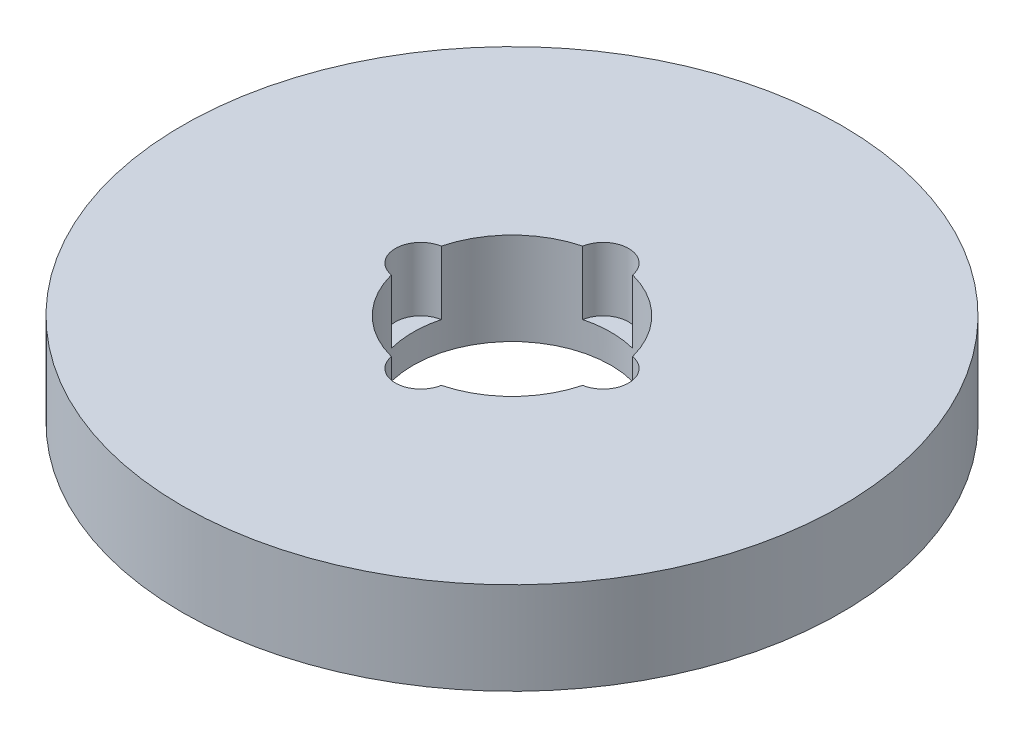
SolidWorks part; units mm, degrees
ref_plane "Front Plane" through (0, 0, 0) normal (0, 0, 1) x (1, 0, 0)
ref_plane "Top Plane" through (0, 0, 0) normal (0, 1, 0) x (1, 0, 0)
ref_plane "Right Plane" through (0, 0, 0) normal (1, 0, 0) x (0, 0, -1)
sketch "Sketch1" plane through (0, 0, 0) normal (0, 1, 0) x (1, 0, 0)
  circle A0 centre (0, 0) radius 25
  dimension "FLANGE_OD" = 50
extrude "Boss-Extrude1" add sketch "Sketch1" along normal blind 7
sketch "Sketch2" plane through (0, 0, 0) normal (0, 1, 0) x (1, 0, 0)
  circle A0 centre (0, 0) radius 7.5
  dimension "BORE_D" = 15
extrude "Cut-Extrude1" cut sketch "Sketch2" along normal through all
sketch "Sketch3" plane through (0, 7, 0) normal (0, 1, 0) x (1, 0, 0)
  circle A0 centre (0, 0) radius 6.9221 construction
  circle A1 centre (-6.9221, 0) radius 1.9224
  dimension "BOLT_D" = 3.8449
  dimension "BOLT_PCD" = 13.8442
extrude "Cut-Extrude2" cut sketch "Sketch3" against normal blind 4.8262
pattern_circular "CirPattern1" count 4 over 360 about axis through (0, 0, 0) along (0, 1, 0) of "Cut-Extrude2"
